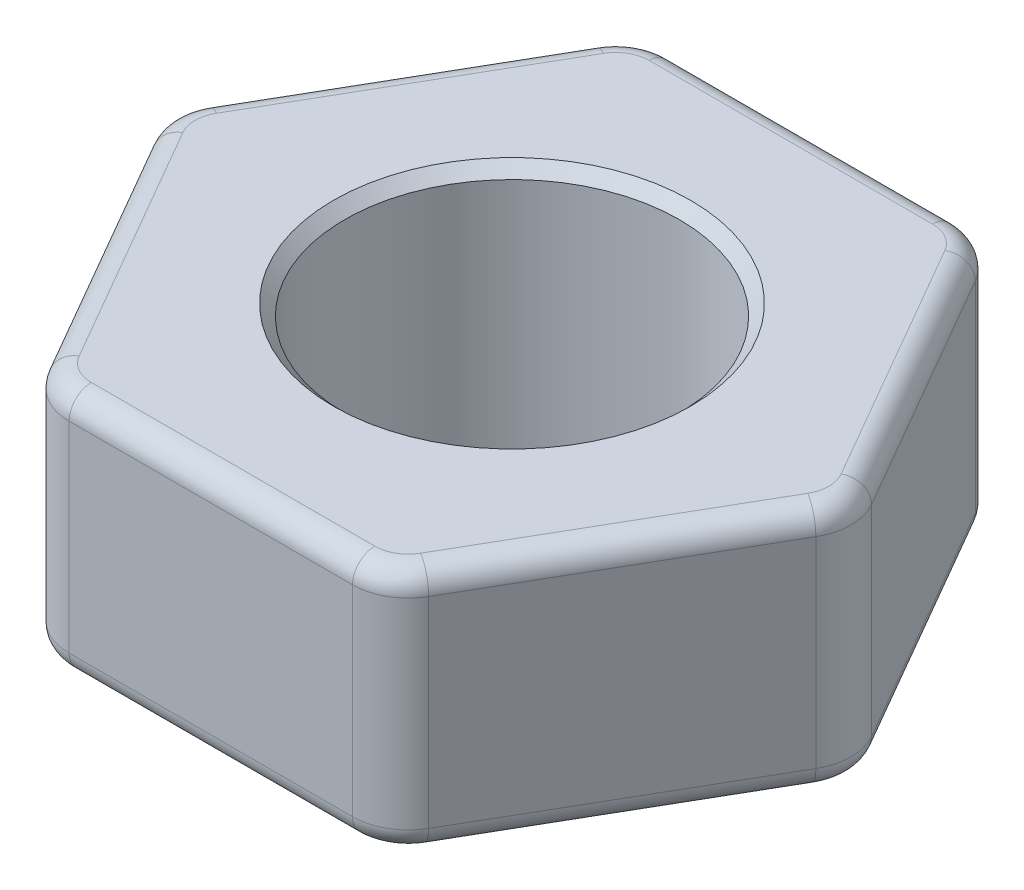
SolidWorks part; units mm, degrees
material "Plain Carbon Steel"
ref_plane "Front Plane" through (0, 0, 0) normal (0, 0, 1) x (1, 0, 0)
ref_plane "Top Plane" through (0, 0, 0) normal (0, 1, 0) x (1, 0, 0)
ref_plane "Right Plane" through (0, 0, 0) normal (1, 0, 0) x (0, 0, -1)
sketch "Sketch1" plane through (0, 0, 0) normal (0, 1, 0) x (1, 0, 0)
  line L1 (3.1177, 0) -> (1.5588, 2.7)
  line L2 (1.5588, 2.7) -> (-1.5588, 2.7)
  line L3 (-1.5588, 2.7) -> (-3.1177, 0)
  line L4 (-3.1177, 0) -> (-1.5588, -2.7)
  line L5 (-1.5588, -2.7) -> (1.5588, -2.7)
  line L6 (1.5588, -2.7) -> (3.1177, 0)
  circle A0 centre (0, 0) radius 2.7 construction
  dimension "D1" = 5.4
extrude "Boss-Extrude1" add sketch "Sketch1" along normal blind 2.2
sketch "Sketch2" plane through (0, 2.2, 0) normal (0, 1, 0) x (1, 0, 0)
  circle A0 centre (0, 0) radius 1.5
  dimension "D1" = 3
extrude "Cut-Extrude1" cut sketch "Sketch2" against normal through all
fillet "Fillet1" radius 0.5 6 edges at (-1.5588, 1.1, 2.7) (-3.1177, 1.1, 0) (-1.5588, 1.1, -2.7) (1.5588, 1.1, -2.7) (3.1177, 1.1, 0) (1.5588, 1.1, 2.7)
fillet "Fillet2" radius 0.2 24 edges at (-3.0403, 0, 0) (-2.3383, 0, -1.35) (-1.5202, 0, -2.633) (0, 0, -2.7) (1.5202, 0, -2.633) (2.3383, 0, -1.35) (3.0403, 0, 0) (2.3383, 0, 1.35) (1.5202, 0, 2.633) (0, 0, 2.7) (-1.5202, 0, 2.633) (-1.5202, 2.2, -2.633) (0, 2.2, -2.7) (1.5202, 2.2, -2.633) (2.3383, 2.2, -1.35) (3.0403, 2.2, 0) (2.3383, 2.2, 1.35) (1.5202, 2.2, 2.633) (0, 2.2, 2.7) (-1.5202, 2.2, 2.633) (-2.3383, 2.2, 1.35) (-3.0403, 2.2, 0) (-2.3383, 0, 1.35) (-2.3383, 2.2, -1.35)
chamfer "Chamfer1" distance 0.1 angle 45 1 edges at (0, 2.2, 1.5)
